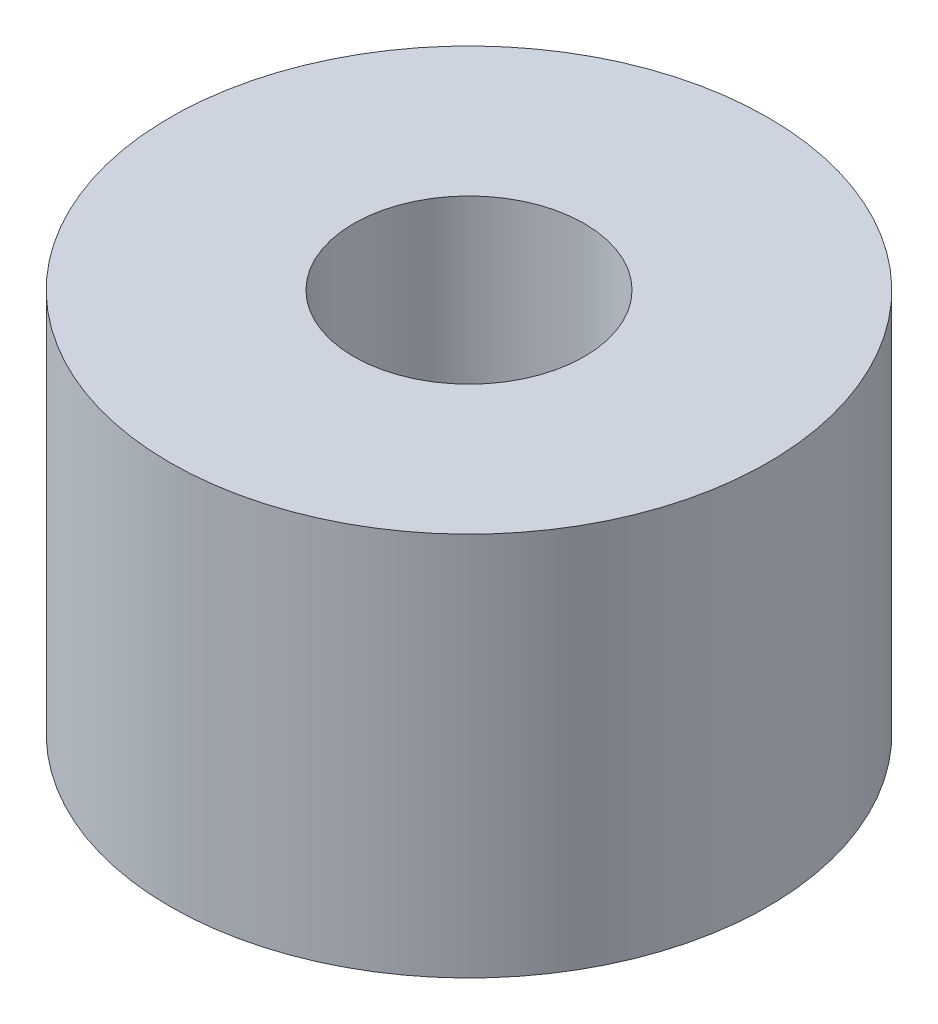
SolidWorks part; units mm, degrees
ref_plane "Front Plane" through (0, 0, 0) normal (0, 0, 1) x (1, 0, 0)
ref_plane "Top Plane" through (0, 0, 0) normal (0, 1, 0) x (1, 0, 0)
ref_plane "Right Plane" through (0, 0, 0) normal (1, 0, 0) x (0, 0, -1)
sketch "Sketch1" plane through (0, 0, 0) normal (0, 1, 0) x (1, 0, 0)
  circle A0 centre (0, 0) radius 22.225
  circle A1 centre (0, 0) radius 8.5725
  dimension "D1" = 44.45
  dimension "D2" = 17.145
extrude "Boss-Extrude1" add sketch "Sketch1" along normal blind 28.575
sketch "Sketch2" plane through (0, 0, 0) normal (0, -1, 0) x (1, 0, 0)
  line L1 (6.9215, 11.9884) -> (-6.9215, 11.9884)
  line L2 (-6.9215, 11.9884) -> (-13.843, 0)
  line L3 (-13.843, 0) -> (-6.9215, -11.9884)
  line L4 (-6.9215, -11.9884) -> (6.9215, -11.9884)
  line L5 (6.9215, -11.9884) -> (13.843, 0)
  line L6 (13.843, 0) -> (6.9215, 11.9884)
  circle A0 centre (0, 0) radius 11.9884 construction
  circle A1 centre (-6.9215, 11.9884) radius 1.5875
  circle A2 centre (6.9215, 11.9884) radius 1.5875
  circle A3 centre (13.843, 0) radius 1.5875
  circle A4 centre (6.9215, -11.9884) radius 1.5875
  circle A5 centre (-6.9215, -11.9884) radius 1.5875
  circle A6 centre (-13.843, 0) radius 1.5875
  point P22 (0, 0)
  circle M3 centre (0, 0) radius 8.5725
  dimension "D2" = 3.175
  dimension "D3" = 6
  dimension "D1" = 13.843
extrude "Cut-Extrude1" cut sketch "Sketch2" against normal blind 9.9219 contours L2 A6 L3 | L3 A6 L2 | A6 L3 A5 L4 A4 L5 A3 L6 A2 L1 A1 L2 M3 | L3 A5 L4 | L4 A5 L3 | L4 A4 L5 | L5 A4 L4 | L5 A3 L6 | L6 A3 L5 | L6 A2 L1 | L1 A2 L6 | L1 A1 L2 | L2 A1 L1 region at (-6.4839, 0, 11.2304) region at (-7.1403, 0, 12.3674) region at (0, 0, 11.634) region at (7.1403, 0, 12.3674) region at (6.4839, 0, 11.2304) region at (-12.9678, 0, 0) region at (-14.2806, 0, 0) region at (14.2806, 0, 0) region at (12.9678, 0, 0) region at (-6.4839, 0, -11.2304) region at (-7.1403, 0, -12.3674) region at (7.1403, 0, -12.3674) region at (6.4839, 0, -11.2304)
fillet "Fillet1" radius 3.175 12 edges at (-13.0493, 4.9609, -1.3748) (-7.7153, 4.9609, -10.6136) (-5.334, 4.9609, -11.9884) (5.334, 4.9609, -11.9884) (7.7152, 4.9609, -10.6136) (13.0492, 4.9609, -1.3748) (13.0493, 4.9609, 1.3748) (7.7153, 4.9609, 10.6136) (5.334, 4.9609, 11.9884) (-5.334, 4.9609, 11.9884) (-7.7153, 4.9609, 10.6136) (-13.0492, 4.9609, 1.3748)
